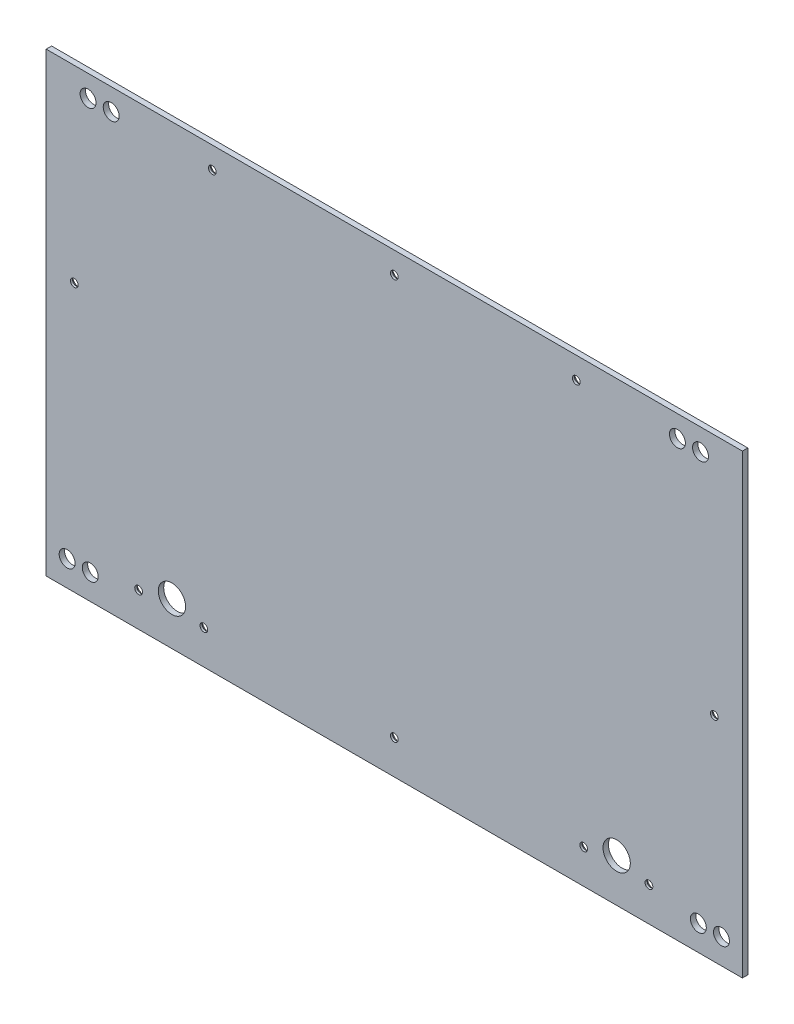
SolidWorks part; units mm, degrees
material "ABS"
ref_plane "X-Y Datum" through (0, 0, 0) normal (0, 0, 1) x (1, 0, 0)
ref_plane "X-Z Datum" through (0, 0, 0) normal (0, 1, 0) x (1, 0, 0)
ref_plane "Y-Z Datum" through (0, 0, 0) normal (1, 0, 0) x (0, 0, -1)
sketch "Sketch1" plane through (0, 0, 0) normal (0, 0, 1) x (1, 0, 0)
  line L0 (-153.025, 98.7125) -> (-153.025, -98.7125)
  line L1 (-153.025, 98.7125) -> (153.025, 98.7125)
  line L2 (-153.025, 98.7125) -> (-153.025, -98.7125)
  line L3 (-153.025, -98.7125) -> (153.025, -98.7125)
  line L4 (153.025, 98.7125) -> (153.025, -98.7125)
  line L5 (-153.025, 98.7125) -> (153.025, -98.7125) construction
  line L6 (-153.025, -98.7125) -> (153.025, 98.7125) construction
  line L7 (-153.025, -98.7125) -> (153.025, -98.7125)
  line L8 (153.025, 98.7125) -> (153.025, -98.7125)
  line L9 (-153.025, 98.7125) -> (153.025, 98.7125)
  circle A0 centre (-142.25, -87.9375) radius 10.775
  circle A1 centre (-118.25, -87.9375) radius 10.775 construction
  circle A2 centre (-130.25, -64.9375) radius 10.775
  point P0 (0, 0)
  dimension "D1" = 21.55
  dimension "D2" = 24
  dimension "D3" = 23
  dimension "D4" = 12
  dimension "D5" = 197.425
  dimension "D6" = 306.05
  dimension "D7" = 0
extrude "Boss-Extrude1" add sketch "Sketch1" along normal blind 2.3813 contours A0 L3 L4 L1 L2 A2 | A2 | A0 | A0 L2 L3 | L9 L0 L7 L8 L1 L4 L3 L2 region at (1.7287, 0.9747, 0) region at (-150.6182, -96.3057, 0) region at (-142.25, -87.9375, 0) region at (-130.25, -64.9375, 0)
sketch "Sketch9" plane through (0, 98.7125, 0) normal (0, 1, 0) x (1, 0, 0)
  line L4 (153.025, 0) -> (-153.025, 0)
  line L5 (-153.025, 0) -> (-153.025, -2.3813)
  line L6 (-153.025, -2.3813) -> (153.025, -2.3813)
  line L7 (153.025, -2.3813) -> (153.025, 0)
  line L8 (153.025, 0) -> (-153.025, 0)
  line L9 (-153.025, 0) -> (-153.025, -2.3813)
  line L10 (-153.025, -2.3813) -> (153.025, -2.3813)
  line L11 (153.025, -2.3813) -> (153.025, 0)
  dimension "D1" = 0
extrude "Boss-Extrude2" add sketch "Sketch9" along normal blind 3.175
sketch "Sketch10" plane through (0, 0, 0) normal (0, 0, -1) x (-1, 0, 0)
  circle A0 centre (-134.61, 92.3625) radius 3.5
  circle A1 centre (-124.45, 92.3625) radius 3.5
  circle A2 centre (-143.8175, -87.5375) radius 3.5
  circle A3 centre (-133.6575, -87.5375) radius 3.5
  point P0 (-143.8175, -87.5375)
  point P1 (-133.6575, -87.5375)
  point P3 (-134.61, 92.3625)
  point P5 (-124.45, 92.3625)
  dimension "D1" = 7
extrude "Cut-Extrude1" cut sketch "Sketch10" against normal through all
mirror "Mirror1" about plane through (0, 0, 0) normal (1, 0, 0) of "Cut-Extrude1"
sketch "Sketch11" plane through (0, 0, 0) normal (0, 0, -1) x (-1, 0, 0)
  point P0 (-111.94, -83.7125)
  point P1 (-83.25, -83.7125)
  point P3 (-140.6875, -4.9375)
  point P5 (-80, 92.3625)
  point P7 (0, 92.3625)
  point P9 (80, 92.3625)
  point P11 (140.6875, 19.0625)
  point P13 (112.402, -83.7125)
  point P15 (83.712, -83.7125)
  point P17 (0, -83.7125)
hole_wizard "CSK for M3 Flat Head Machine Screw1" positions "Sketch11" profile "Sketch12" countersink size "M3" standard "ANSI Metric" end condition through all
sketch "Sketch12" plane through (111.94, -83.7125, 0) normal (1, 0, 0) x (0, 1, 0)
  line L0 (0, 0) -> (0, 2.3812)
  line L1 (0, 2.3812) -> (1.7, 2.3812)
  line L2 (1.7, 2.3812) -> (1.7, 1.45)
  line L3 (1.7, 1.45) -> (3.15, 0)
  line L5 (3.15, 0) -> (0, 0)
  line L6 (-1.7, 1.45) -> (-3.15, 0) construction
  line L11 (0, -6.35) -> (0, 107.95) construction
  dimension "Thru Hole Dia." = 3.4
  dimension "Thru Hole Depth" = 2.3813
  dimension "Near C'Sink Dia." = 6.3
  dimension "Near C'Sink Angle" = 90
sketch "Sketch13" plane through (0, 0, 0) normal (0, 0, -1) x (-1, 0, 0)
  circle A0 centre (-97.75, -79.7125) radius 6 construction
  circle A1 centre (97.75, -79.7125) radius 6 construction
  circle A2 centre (-97.75, -79.7125) radius 6
  circle A3 centre (97.75, -79.7125) radius 6
extrude "Cut-Extrude2" cut sketch "Sketch13" against normal through all
